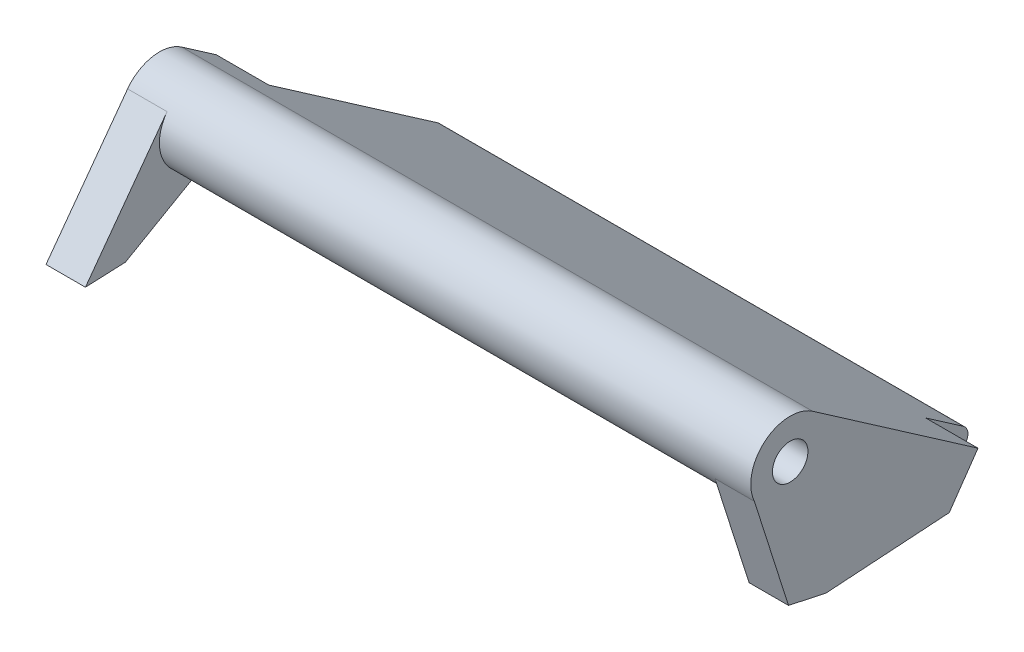
SolidWorks part; units mm, degrees
ref_plane "前视基准面" through (0, 0, 0) normal (0, 0, 1) x (1, 0, 0)
ref_plane "上视基准面" through (0, 0, 0) normal (0, 1, 0) x (1, 0, 0)
ref_plane "右视基准面" through (0, 0, 0) normal (1, 0, 0) x (0, 0, -1)
other "Configuration Table"
sketch "草图1" plane through (0, 0, 0) normal (1, 0, 0) x (0, 0, -1)
  line L2 (8.9174, -4.3583) -> (8.4877, -4.9779)
  line L3 (8.4877, -4.9779) -> (0.8971, 0.2857)
  line L4 (0.8971, 0.2857) -> (0.4245, 0.2857)
  line L5 (0.4245, 0.2857) -> (0.4245, 1.4387)
  line L6 (0.8548, 1.2326) -> (8.9174, -4.3583)
  circle A0 centre (0, 0) radius 0.675
  circle A1 centre (0, 0) radius 1.5
  dimension "D1" = 1.35
  dimension "D2" = 3
extrude "凸台-拉伸1" add sketch "草图1" along normal mid plane 24 contours A1 L3 L4 A0 L5 | A1 L3 L2 | L3 A1 L5 A0 L4 region at (0, -2.1271, -5.0505) region at (0, 0.671, -0.9097) region at (0, -0.8219, 1.2038)
sketch "草图2" plane through (0, 0, 0) normal (0, 1, 0) x (1, 0, 0)
  line L0 (0, -3.6448) -> (0, 3.6448) construction
  line L2 (-10.0026, 13.1501) -> (-10.0026, 2.1657)
  line L5 (0, -5.6821) -> (0, 3.4028) construction
  line L6 (10.0026, 13.1501) -> (10.0026, 2.1657)
  line L10 (-10.0026, 2.1657) -> (-12.5088, 2.1657)
  line L11 (-12.5088, 2.1657) -> (-12.5088, 13.1501)
  line L12 (-12.5088, 13.1501) -> (-10.0026, 13.1501)
  line L13 (12.5088, 13.1501) -> (10.0026, 13.1501)
  line L14 (12.5088, 2.1657) -> (12.5088, 13.1501)
  line L15 (10.0026, 2.1657) -> (12.5088, 2.1657)
  point P0 (0, 10.0705)
extrude "切除-拉伸1" cut sketch "草图2" against normal blind 10 and the other way blind 10
sketch "草图3" plane through (-12, 0, 0) normal (-1, 0, 0) x (0, 0, 1)
  line L0 (1.2095, 0.8871) -> (4.3151, -3.347)
  line L1 (4.3151, -3.347) -> (2.7911, -3.2816)
  line L2 (2.7911, -3.2816) -> (-0.4158, -1.4412)
  arc A0 (-1.4945, -0.1286) -> (-0.8548, 1.2326) centre (0, 0) ccw construction
  arc A1 (-0.4158, -1.4412) -> (1.2095, 0.8871) centre (0, 0) ccw
extrude "凸台-拉伸2" add sketch "草图3" against normal blind 1.5
fillet "圆角1" radius 0.4 2 edges at (0, -4.9779, -8.4877) (0, -4.3583, -8.9174)
sketch "草图4" plane through (12, 0, 0) normal (1, 0, 0) x (0, 0, -1)
  line L0 (-1.3616, -0.6293) -> (-0.0648, -4.7068)
  line L1 (-0.0648, -4.7068) -> (1.3583, -5.0142)
  line L5 (6.0526, -4.7068) -> (1.3583, -5.0142)
  line L6 (2.1657, -0.594) -> (6.0526, -4.7068)
  line L7 (2.1657, -0.594) -> (2.1657, 0.3236) construction
  line L8 (1.4945, -0.1286) -> (2.1657, -0.594)
  arc A0 (0.8548, 1.2326) -> (1.4945, -0.1286) centre (0, 0) ccw construction
  arc A1 (-1.3616, -0.6293) -> (1.4945, -0.1286) centre (0, 0) ccw
extrude "凸台-拉伸3" add sketch "草图4" against normal blind 1.5
sketch "草图5" plane through (10.0026, 0, 0) normal (1, 0, 0) x (0, 0, -1)
  line L0 (6.0526, -4.7068) -> (2.1657, -0.594) construction
  line L1 (2.1657, -0.594) -> (2.1657, 0.3236) construction
  line L2 (6.0526, -4.7068) -> (2.1657, -0.594)
  line L3 (2.1657, -0.594) -> (2.1657, 0.3236)
  line L4 (6.0526, -4.7068) -> (7.1461, -3.1299)
  line L5 (2.1657, 0.3236) -> (8.5887, -4.1303) construction
  line L6 (7.1461, -3.1299) -> (2.1657, 0.3236)
extrude "凸台-拉伸4" add sketch "草图5" along normal up to surface (1.9974 mm away) up to face at (12, -1.8926, -1.4942)
